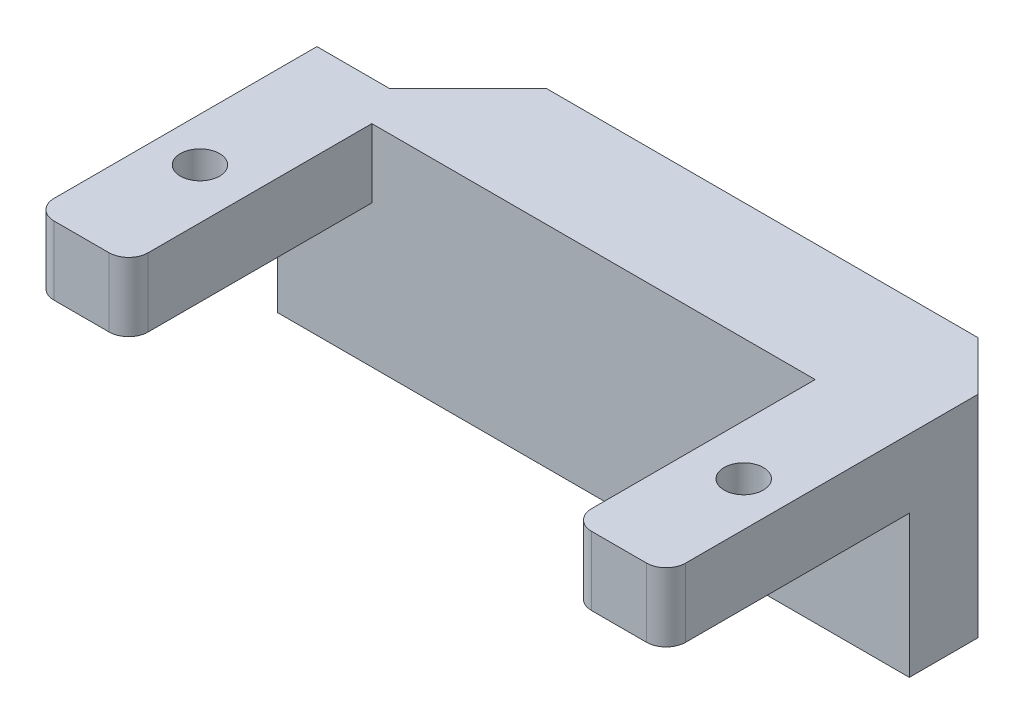
SolidWorks part; units mm, degrees
ref_plane "Front Plane" through (0, 0, 0) normal (0, 0, 1) x (1, 0, 0)
ref_plane "Top Plane" through (0, 0, 0) normal (0, 1, 0) x (1, 0, 0)
ref_plane "Right Plane" through (0, 0, 0) normal (1, 0, 0) x (0, 0, -1)
sketch "Sketch1" plane through (0, 0, 0) normal (0, 0, 1) x (1, 0, 0)
  line L1 (-16.1, 12.75) -> (16.1, 12.75)
  line L2 (-16.1, 12.75) -> (-16.1, -12.75)
  line L3 (-16.1, -12.75) -> (16.1, -12.75)
  line L4 (16.1, 12.75) -> (16.1, -12.75)
  line L5 (-16.1, 12.75) -> (16.1, -12.75) construction
  line L6 (-16.1, -12.75) -> (16.1, 12.75) construction
  point P0 (0, 0)
  dimension "D1" = 32.2
  dimension "D2" = 25.5
extrude "Boss-Extrude1" add sketch "Sketch1" along normal blind 14.4
sketch "Sketch3" plane through (0, 0, 14.4) normal (0, 0, 1) x (1, 0, 0)
  line L0 (-16.1, 12.75) -> (-16.1, -12.75) construction
  line L1 (-16.1, 10.75) -> (16.1, 10.75)
  line L2 (-16.1, 10.75) -> (-16.1, -11)
  line L3 (-16.1, -11) -> (16.1, -11)
  line L4 (16.1, 10.75) -> (16.1, -11)
  line L5 (16.1, -12.75) -> (16.1, 12.75) construction
  line L6 (16.1, 12.75) -> (-16.1, 12.75) construction
  dimension "D1" = 2
  dimension "D2" = 21.75
extrude "Cut-Extrude1" cut sketch "Sketch3" against normal blind 12.4
sketch "Sketch5" plane through (0, 0, 14.4) normal (0, 0, 1) x (1, 0, 0)
  line L0 (16.1, 12.75) -> (-16.1, 12.75) construction
  line L1 (-11.3, 12.75) -> (11.3, 12.75)
  line L2 (-11.3, 12.75) -> (-11.3, 10.75)
  line L3 (-11.3, 10.75) -> (11.3, 10.75)
  line L4 (11.3, 12.75) -> (11.3, 10.75)
  line L5 (16.1, 10.75) -> (-16.1, 10.75) construction
  line L6 (-16.1, 12.75) -> (-16.1, 10.75) construction
  line L7 (16.1, 10.75) -> (16.1, 12.75) construction
  dimension "D1" = 4.8
  dimension "D2" = 4.8
extrude "Cut-Extrude2" cut sketch "Sketch5" against normal blind 14.4 contours L2 L1 L4 L3
fillet "Fillet1" radius 1 1 edges at (-11.3, 11.75, 14.4)
fillet "Fillet2" radius 1 1 edges at (-16.1, 11.75, 14.4)
fillet "Fillet3" radius 1 1 edges at (11.3, 11.75, 14.4)
fillet "Fillet4" radius 1 1 edges at (16.1, 11.75, 14.4)
sketch "Sketch10" plane through (0, 12.75, 0) normal (0, 1, 0) x (1, 0, 0)
  line L0 (-16.1, -13.4) -> (-16.1, 0) construction
  circle A0 centre (-13.86, -8.203) radius 1
  dimension "D1" = 2.24
extrude "Cut-Extrude3" cut sketch "Sketch10" against normal blind 10
mirror "Mirror1" about plane through (0, 0, 0) normal (1, 0, 0) of "Cut-Extrude3"
sketch "Sketch11" plane through (0, 0, 14.4) normal (0, 0, 1) x (1, 0, 0)
  line L0 (-16.1, -12.75) -> (16.1, -12.75) construction
  line L1 (-16.1, -11) -> (-11.25, -11)
  line L2 (-16.1, -11) -> (-16.1, -12.75)
  line L3 (-16.1, -12.75) -> (-11.25, -12.75)
  line L4 (-11.25, -11) -> (-11.25, -12.75)
  dimension "D1" = 4.85
extrude "Cut-Extrude4" cut sketch "Sketch11" against normal blind 20
mirror "Mirror2" about plane through (0, 0, 0) normal (1, 0, 0) of "Cut-Extrude4"
fillet "Fillet5" radius 1 6 edges at (-11.25, -11.875, 0) (-16.1, -11, 1) (16.1, -11, 1) (11.25, -11.875, 0) (11.25, -11.875, 14.4) (-11.25, -11.875, 14.4)
sketch "Sketch12" plane through (0, 0, 0) normal (0, 0, -1) x (-1, 0, 0)
  line L1 (-12.6, 5.5) -> (7.4, 5.5)
  line L2 (-12.6, 5.5) -> (-12.6, 3.5)
  line L3 (-12.6, 3.5) -> (7.4, 3.5)
  line L4 (7.4, 5.5) -> (7.4, 3.5)
  line L6 (11.3, 10.75) -> (-11.3, 10.75) construction
  line L9 (-16.1, -10) -> (-16.1, 12.75) construction
  dimension "D1" = 5.25
  dimension "D2" = 2
  dimension "D3" = 20
  dimension "D4" = 3.5
extrude "Boss-Extrude2" add sketch "Sketch12" along normal blind 5
sketch "Sketch13" plane through (0, 0, 0) normal (0, 0, -1) x (-1, 0, 0)
  line L0 (7.4, 5.5) -> (-12.6, 5.5) construction
  line L1 (-12.6, 9) -> (7.4, 9)
  line L2 (-12.6, 9) -> (-12.6, 7)
  line L3 (-11.6, 7) -> (6.4, 7)
  line L4 (7.4, 9) -> (7.4, 7)
  line L5 (-2.6, 7) -> (-2.6, 5.5) construction
  line L7 (-12.6, 7) -> (-12.6, 5.5)
  line L8 (-12.6, 5.5) -> (-11.6, 5.5)
  line L9 (-11.6, 7) -> (-11.6, 5.5)
  line L10 (7.4, 5.5) -> (-12.6, 5.5) construction
  line L11 (7.4, 5.5) -> (6.4, 5.5)
  line L12 (6.4, 7) -> (6.4, 5.5)
  line L14 (7.4, 7) -> (7.4, 5.5)
  dimension "D1" = 1.5
  dimension "D2" = 1
extrude "Boss-Extrude3" add sketch "Sketch13" along normal blind 5
sketch "Sketch14" plane through (0, 3.5, 0) normal (0, -1, 0) x (1, 0, 0)
  line L1 (-19.2363, 15.8932) -> (18.6063, 15.8932)
  line L2 (-19.2363, 15.8932) -> (-19.2363, -6.2412)
  line L3 (-19.2363, -6.2412) -> (18.6063, -6.2412)
  line L4 (18.6063, 15.8932) -> (18.6063, -6.2412)
extrude "Cut-Extrude5" cut sketch "Sketch14" along normal through all
sketch "Sketch15" plane through (0, 12.75, 0) normal (0, 1, 0) x (1, 0, 0)
  line L0 (-7.4, 0) -> (12.6, 0) construction
  line L1 (12.6, 0) -> (12.6, 5) construction
  line L2 (12.6, 5) -> (-7.4, 5) construction
  line L3 (-7.4, 5) -> (-7.4, 0) construction
  line L4 (-11.3, -2) -> (11.3, -2) construction
  line L5 (11.3, -2) -> (11.3, 0) construction
  line L6 (11.3, 0) -> (-11.3, 0) construction
  line L7 (-11.3, 0) -> (-11.3, -2) construction
  line L8 (11.3, 0) -> (12.6, 0)
  line L9 (12.6, 0) -> (12.6, 5)
  line L10 (12.6, 5) -> (-7.4, 5)
  line L11 (-7.4, 5) -> (-7.4, 0)
  line L12 (-11.3, -2) -> (11.3, -2)
  line L13 (11.3, -2) -> (11.3, 0)
  line L14 (-7.4, 0) -> (-11.3, 0)
  line L15 (-11.3, 0) -> (-11.3, -2)
extrude "Boss-Extrude5" add sketch "Sketch15" against normal up to surface (3.75 mm away) up to face at (2.6, 9, -2.5)
chamfer "Chamfer1" distance 5 angle 45 2 edges at (-7.4, 8.125, 0) (12.6, 8.125, 0)
sketch "Sketch16" plane through (0, 12.75, 0) normal (0, 1, 0) x (1, 0, 0)
  line L11 (16.1, -13.4) -> (16.1, 1.5)
  line L12 (16.1, 1.5) -> (12.6, 5)
  line L13 (12.6, 5) -> (-7.4, 5)
  line L14 (-7.4, 5) -> (-12.4, 0)
  line L15 (-12.4, 0) -> (-16.1, 0)
  line L16 (-16.1, 0) -> (-16.1, -13.4)
  line L17 (-15.1, -14.4) -> (-12.3, -14.4)
  line L18 (-11.3, -13.4) -> (-11.3, -2)
  line L19 (-11.3, -2) -> (11.3, -2)
  line L20 (11.3, -2) -> (11.3, -13.4)
  line L21 (12.3, -14.4) -> (15.1, -14.4)
  line L22 (16.1, -13.4) -> (16.1, 1.5)
  line L23 (16.1, 1.5) -> (12.6, 5)
  line L24 (12.6, 5) -> (-7.4, 5)
  line L25 (-7.4, 5) -> (-12.4, 0)
  line L26 (-12.4, 0) -> (-16.1, 0)
  line L27 (-16.1, 0) -> (-16.1, -13.4)
  line L28 (-15.1, -14.4) -> (-12.3, -14.4)
  line L29 (-11.3, -13.4) -> (-11.3, -2)
  line L30 (-11.3, -2) -> (11.3, -2)
  line L31 (11.3, -2) -> (11.3, -13.4)
  line L32 (12.3, -14.4) -> (15.1, -14.4)
  circle A0 centre (13.86, -8.203) radius 1 construction
  circle A1 centre (-13.86, -8.203) radius 1 construction
  circle A2 centre (13.86, -8.203) radius 1
  circle A3 centre (-13.86, -8.203) radius 1
  arc A4 (-16.1, -13.4) -> (-15.1, -14.4) centre (-15.1, -13.4) ccw
  arc A5 (-12.3, -14.4) -> (-11.3, -13.4) centre (-12.3, -13.4) ccw
  arc A6 (11.3, -13.4) -> (12.3, -14.4) centre (12.3, -13.4) ccw
  arc A7 (15.1, -14.4) -> (16.1, -13.4) centre (15.1, -13.4) ccw
  arc A8 (-16.1, -13.4) -> (-15.1, -14.4) centre (-15.1, -13.4) ccw
  arc A9 (-12.3, -14.4) -> (-11.3, -13.4) centre (-12.3, -13.4) ccw
  arc A10 (11.3, -13.4) -> (12.3, -14.4) centre (12.3, -13.4) ccw
  arc A11 (15.1, -14.4) -> (16.1, -13.4) centre (15.1, -13.4) ccw
  dimension "D1" = 0
extrude "Boss-Extrude6" add sketch "Sketch16" along normal blind 1.5
sketch "Sketch17" plane through (0, 0, -5) normal (0, 0, -1) x (-1, 0, 0)
  line L1 (-18.3963, 20.4042) -> (13.5242, 20.4042)
  line L2 (-18.3963, 20.4042) -> (-18.3963, -1.8562)
  line L3 (-18.3963, -1.8562) -> (13.5242, -1.8562)
  line L4 (13.5242, 20.4042) -> (13.5242, -1.8562)
extrude "Cut-Extrude6" cut sketch "Sketch17" against normal blind 1
scale "Scale1" scale about centroid uniform scaling yes scale factor 1.02
